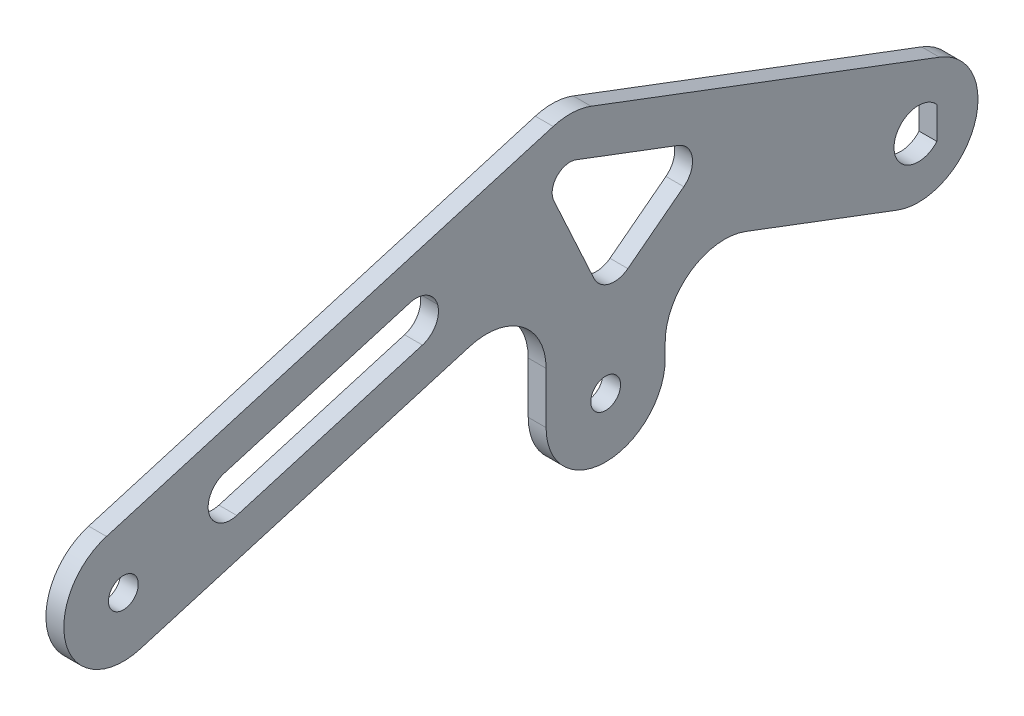
SolidWorks part; units mm, degrees
ref_plane "Front Plane" through (0, 0, 0) normal (0, 0, 1) x (1, 0, 0)
ref_plane "Top Plane" through (0, 0, 0) normal (0, 1, 0) x (1, 0, 0)
ref_plane "Right Plane" through (0, 0, 0) normal (1, 0, 0) x (0, 0, -1)
sketch "Sketch4" plane through (0, 0, 0) normal (1, 0, 0) x (0, 0, -1)
  line L0 (92.5, 20) -> (153.5, 20) construction
  line L1 (0, 0) -> (153.5, 0) construction
  line L2 (0, 0) -> (0, 20) construction
  line L3 (0, 20) -> (77.5, 20) construction
  line L4 (153.5, 0) -> (153.5, 20) construction
  line L6 (77.5, 20) -> (77.5, 39.6162) construction
  line L7 (77.5, 39.6162) -> (92.5, 39.6162) construction
  line L8 (92.5, 20) -> (92.5, 39.6162) construction
  circle A0 centre (10, 10) radius 2.5 construction
  circle A1 centre (143.5, 10) radius 2.5 construction
  circle A2 centre (85, 32.1162) radius 3 construction
  dimension "D2" = 5
  dimension "D3" = 5
  dimension "D4" = 133.5
  dimension "D5" = 10
  dimension "D7" = 10
  dimension "D8" = 10
  dimension "D10" = 6
  dimension "D12" = 7.5
  dimension "D13" = 22.1162
  dimension "D14" = 75
  dimension "D1" = 20
  dimension "D6" = 10
  dimension "D9" = 15
  dimension "D11" = 7.5
sketch "Sketch3" plane through (0, 0, 0) normal (1, 0, 0) x (0, 0, -1)
  line L14 (7.1716, 19.5917) -> (82.1716, 41.7079)
  line L18 (12.8284, 0.4083) -> (80.9802, 20.5051)
  line L22 (100.9802, 15.384) -> (139.9637, 0.6461)
  line L23 (147.0363, 19.3539) -> (88.5363, 41.4701)
  line L25 (80.9802, 20.5051) -> (80.9802, -1.4935)
  line L26 (100.9802, 15.384) -> (100.9802, -1.4935)
  line L27 (146.6, 12.6833) -> (146.6, 7.3167)
  circle A2 centre (85, 32.1162) radius 3
  arc A3 (7.1716, 19.5917) -> (12.8284, 0.4083) centre (10, 10) ccw
  arc A6 (88.5363, 41.4701) -> (82.1716, 41.7079) centre (85, 32.1162) ccw
  arc A7 (139.9637, 0.6461) -> (147.0363, 19.3539) centre (143.5, 10) ccw
  arc A8 (80.9802, -1.4935) -> (100.9802, -1.4935) centre (90.9802, -1.4935) ccw
  circle A9 centre (90.9802, -1.4935) radius 2.5
  circle A10 centre (10, 10) radius 2.5
  arc A11 (146.6, 12.6833) -> (146.6, 7.3167) centre (143.5, 10) ccw
  dimension "D2" = 8.2
  dimension "D3" = 3.1
  dimension "D4" = 20
  dimension "D5" = 20
  dimension "D7" = 33.6097
  dimension "D8" = 5.9802
  dimension "D10" = 5
  dimension "D9" = 5
  dimension "D6" = 20
  dimension "D1" = 20
extrude "Boss-Extrude2" add sketch "Sketch3" along normal blind 3
fillet "Fillet1" radius 10 2 edges at (1.5, 15.384, -100.9802) (1.5, 20.5051, -80.9802)
ref_plane "Min 34.36" through (0, -31.4884, -7.6473) normal (0, -0.9718, -0.236) x (-1, 0, 0)
ref_plane "Max 141.51" through (0, 61.7296, -103.5497) normal (0, 0.5121, -0.859) x (-1, 0, 0)
ref_plane "Max 18.41" through (0, -68.9516, -79.9112) normal (0, 0.6533, 0.7571) x (-1, 0, 0)
ref_plane "Min 23.86" through (0, 67.8436, -88.3815) normal (0, 0.6089, -0.7932) x (-1, 0, 0)
sketch "Sketch5" plane through (0, 0, 0) normal (1, 0, 0) x (0, 0, -1)
  line L0 (23.3268, 17.8395) -> (61.6935, 29.1532)
  line L1 (61.6935, 29.1532) -> (63.8148, 21.9594)
  line L2 (63.8148, 21.9594) -> (25.4482, 10.6458)
  line L3 (25.4482, 10.6458) -> (23.3268, 17.8395)
  line L5 (82.1716, 41.7079) -> (7.1716, 19.5917) construction
  line L6 (86.0609, 34.9224) -> (109.4455, 26.0817)
  line L7 (109.4455, 26.0817) -> (90.9802, 11.9104)
  line L8 (90.9802, 11.9104) -> (82.2739, 30.864)
  line L9 (147.0363, 19.3539) -> (88.5363, 41.4701) construction
  line L10 (80.9802, 7.1306) -> (80.9802, -1.4935) construction
  circle A1 centre (10, 10) radius 2.5 construction
  circle A2 centre (85, 32.1162) radius 3 construction
  arc A3 (86.0609, 34.9224) -> (82.2739, 30.864) centre (85, 32.1162) ccw
  dimension "D3" = 15
  dimension "D1" = 7.5
  dimension "D2" = 6.25
  dimension "D4" = 40
  dimension "D5" = 10
  dimension "D6" = 25
  dimension "D7" = 18.9535
extrude "Cut-Extrude1" cut sketch "Sketch5" along normal blind 10
fillet "Fillet2" radius 3.75 6 edges at (1.5, 11.9104, -90.9802) (1.5, 26.0817, -109.4455) (1.5, 29.1532, -61.6935) (1.5, 21.9594, -63.8148) (1.5, 10.6458, -25.4482) (1.5, 17.8395, -23.3268)
